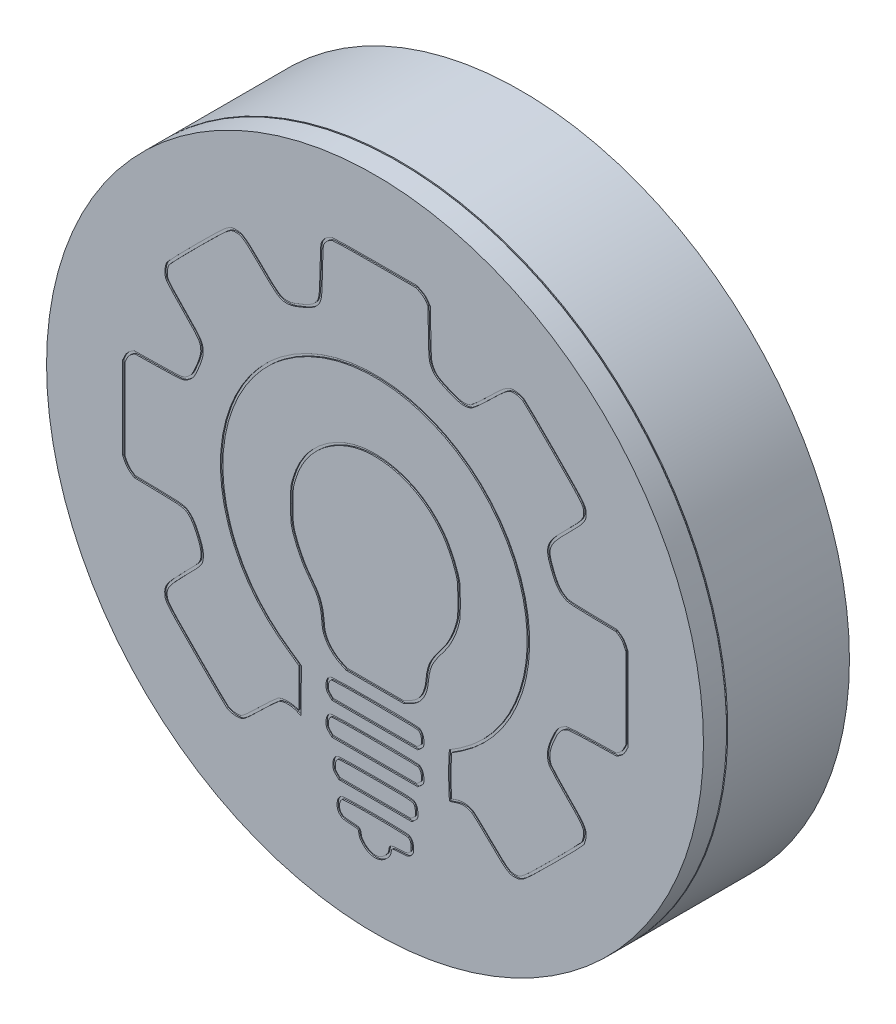
SolidWorks part; units mm, degrees
ref_plane "Front Plane" through (0, 0, 0) normal (0, 0, 1) x (1, 0, 0)
ref_plane "Top Plane" through (0, 0, 0) normal (0, 1, 0) x (1, 0, 0)
ref_plane "Right Plane" through (0, 0, 0) normal (1, 0, 0) x (0, 0, -1)
sketch "Sketch1" plane through (0, 0, 0) normal (0, 0, 1) x (1, 0, 0)
  circle A0 centre (0, 0) radius 25.025
  circle A1 centre (0, 0) radius 27
  dimension "D1" = 50.05
  dimension "D2" = 54
extrude "Boss-Extrude1" add sketch "Sketch1" along normal blind 10
sketch "Sketch2" plane through (0, 0, 10) normal (0, 0, 1) x (1, 0, 0)
  circle A0 centre (0, 0) radius 27
  circle A1 centre (0, 0) radius 27 construction
  point P8 (0, 0)
  circle M3 centre (0, 0) radius 27
  circle M4 centre (0, 0) radius 25.025
extrude "Boss-Extrude3" add sketch "Sketch2" along normal blind 2 contours M3 M4 | M4 region at (-26.2363, 0, 10) region at (0, 0, 10)
sketch "Sketch4" plane through (0, 0, 12) normal (0, 0, 1) x (1, 0, 0)
  line L0 (-17.8576, 4.6203) -> (-19.805, 4.585)
  line L1 (-19.805, 4.585) -> (-20.1013, 4.3874)
  line L2 (-20.574, 3.823) -> (-20.7433, 3.4561)
  line L3 (-20.7433, 3.4561) -> (-20.7433, 0.0624)
  line L4 (-20.7433, 0.0624) -> (-20.7433, -3.3243)
  line L5 (-20.7433, -3.3243) -> (-20.567, -3.6841)
  line L6 (-20.0942, -4.2415) -> (-19.805, -4.4461)
  line L7 (-19.805, -4.4461) -> (-17.8576, -4.4814)
  line L8 (-6.3994, -14.4086) -> (-6.0678, -14.5638)
  line L9 (-6.0678, -14.5638) -> (-6.0678, -12.7999)
  line L10 (17.9282, -4.4884) -> (19.8755, -4.4461)
  line L11 (19.8755, -4.4461) -> (20.1577, -4.2556)
  line L12 (20.6305, -3.6982) -> (20.8139, -3.3243)
  line L13 (20.8139, -3.3243) -> (20.8139, 0.0624)
  line L14 (20.8139, 0.0624) -> (20.8139, 3.4561)
  line L15 (20.8139, 3.4561) -> (20.6446, 3.823)
  line L16 (20.1718, 4.3874) -> (19.8755, 4.585)
  line L17 (19.8755, 4.585) -> (17.9282, 4.6203)
  line L18 (4.5861, 17.9976) -> (4.5508, 19.9097)
  line L19 (4.5508, 19.9097) -> (4.3603, 20.1919)
  line L20 (3.8029, 20.6646) -> (3.429, 20.8481)
  line L21 (3.429, 20.8481) -> (0.0423, 20.841)
  line L22 (-2.8363, -9.2298) -> (-2.3636, -9.4556)
  line L23 (-2.3636, -9.4556) -> (0, -9.4556)
  line L24 (0, -9.4556) -> (2.3636, -9.4556)
  line L25 (2.3636, -9.4556) -> (2.8363, -9.2298)
  line L26 (-3.7818, -11.9321) -> (-3.5419, -12.1719)
  line L27 (-3.5419, -12.1719) -> (-0.0071, -12.1719)
  line L28 (-0.0071, -12.1719) -> (3.5207, -12.1719)
  line L29 (3.5207, -12.1719) -> (3.7747, -11.9532)
  line L30 (-3.7818, -14.5629) -> (-3.5419, -14.8028)
  line L31 (-3.5419, -14.8028) -> (-0.0071, -14.8028)
  line L32 (-0.0071, -14.8028) -> (3.5207, -14.8028)
  line L33 (3.5207, -14.8028) -> (3.7747, -14.5841)
  line L34 (-3.2173, -17.2943) -> (-2.9774, -17.5342)
  line L35 (-2.9774, -17.5342) -> (0.0282, -17.5342)
  line L36 (0.0282, -17.5342) -> (3.0268, -17.5342)
  line L37 (3.0268, -17.5342) -> (3.2808, -17.3155)
  line L76 (-17.854, 4.4203) -> (-19.7428, 4.3861)
  line L77 (-19.7428, 4.3861) -> (-19.989, 4.2219)
  line L78 (-20.3932, 3.7376) -> (-20.5433, 3.4122)
  line L79 (-20.5433, 3.4122) -> (-20.5433, 0.0624)
  line L80 (-20.5433, 0.0624) -> (-20.5433, -3.2779)
  line L81 (-20.5433, -3.2779) -> (-20.3881, -3.5947)
  line L82 (-19.9817, -4.0761) -> (-19.7398, -4.2473)
  line L83 (-19.7398, -4.2473) -> (-17.854, -4.2814)
  line L84 (-6.3165, -14.2265) -> (-6.2678, -14.2493)
  line L85 (-6.2678, -14.2493) -> (-6.2678, -12.7999)
  line L86 (17.9238, -4.2885) -> (19.8124, -4.2474)
  line L87 (19.8124, -4.2474) -> (20.0471, -4.089)
  line L88 (20.4516, -3.6088) -> (20.6139, -3.2779)
  line L89 (20.6139, -3.2779) -> (20.6139, 0.0624)
  line L90 (20.6139, 0.0624) -> (20.6139, 3.4122)
  line L91 (20.6139, 3.4122) -> (20.4637, 3.7376)
  line L92 (20.0596, 4.2219) -> (19.8133, 4.3861)
  line L93 (19.8133, 4.3861) -> (17.9243, 4.4203)
  line L94 (4.3861, 17.9939) -> (4.352, 19.8468)
  line L95 (4.352, 19.8468) -> (4.1937, 20.0812)
  line L96 (3.7135, 20.4857) -> (3.3828, 20.648)
  line L97 (3.3828, 20.648) -> (0.0423, 20.641)
  line L98 (-2.7503, -9.0492) -> (-2.3183, -9.2556)
  line L99 (-2.3183, -9.2556) -> (0, -9.2556)
  line L100 (0, -9.2556) -> (2.3183, -9.2556)
  line L101 (2.3183, -9.2556) -> (2.7507, -9.0491)
  line L102 (-3.6404, -11.7906) -> (-3.459, -11.9719)
  line L103 (-3.459, -11.9719) -> (-0.0071, -11.9719)
  line L104 (-0.0071, -11.9719) -> (3.4465, -11.9719)
  line L105 (3.4465, -11.9719) -> (3.6424, -11.8032)
  line L106 (-3.6404, -14.4215) -> (-3.459, -14.6028)
  line L107 (-3.459, -14.6028) -> (-0.0071, -14.6028)
  line L108 (-0.0071, -14.6028) -> (3.4465, -14.6028)
  line L109 (3.4465, -14.6028) -> (3.6424, -14.4341)
  line L110 (-3.0759, -17.1529) -> (-2.8946, -17.3342)
  line L111 (-2.8946, -17.3342) -> (0.0282, -17.3342)
  line L112 (0.0282, -17.3342) -> (2.9526, -17.3342)
  line L113 (2.9526, -17.3342) -> (3.1485, -17.1655)
  spline S0 degree 3 poles (-3.5631, 20.7634) (-3.8876, 20.6435) (-4.1346, 20.4459) (-4.318, 20.1566) knots 0 0 0 0 1 1 1 1
  spline S1 degree 3 poles (-4.318, 20.1566) (-4.4732, 19.9026) (-4.4803, 19.825) (-4.5156, 17.9906) knots 0 0 0 0 1 1 1 1
  spline S2 degree 3 poles (-4.5156, 17.9906) (-4.5579, 15.888) (-4.5791, 15.7822) (-5.0236, 15.3377) knots 0 0 0 0 1 1 1 1
  spline S3 degree 3 poles (-5.0236, 15.3377) (-5.3128, 15.0413) (-6.5758, 14.4981) (-7.0767, 14.4416) knots 0 0 0 0 1 1 1 1
  spline S4 degree 3 poles (-7.0767, 14.4416) (-7.6976, 14.3781) (-7.9163, 14.5263) (-9.2851, 15.888) knots 0 0 0 0 1 1 1 1
  spline S5 degree 3 poles (-9.2851, 15.888) (-10.5622, 17.158) (-10.8797, 17.3838) (-11.3595, 17.3908) knots 0 0 0 0 1 1 1 1
  spline S6 degree 3 poles (-11.3595, 17.3908) (-12.0086, 17.3908) (-12.0297, 17.3767) (-14.5556, 14.865) knots 0 0 0 0 1 1 1 1
  spline S7 degree 3 poles (-14.5556, 14.865) (-15.868, 13.5526) (-17.0039, 12.3885) (-17.0815, 12.2615) knots 0 0 0 0 1 1 1 1
  spline S8 degree 3 poles (-17.0815, 12.2615) (-17.265, 11.9651) (-17.3285, 11.4148) (-17.2156, 11.0691) knots 0 0 0 0 1 1 1 1
  spline S9 degree 3 poles (-17.2156, 11.0691) (-17.145, 10.8645) (-16.7852, 10.4482) (-15.7974, 9.4463) knots 0 0 0 0 1 1 1 1
  spline S10 degree 3 poles (-15.7974, 9.4463) (-14.3933, 8.0211) (-14.3228, 7.9152) (-14.3228, 7.252) knots 0 0 0 0 1 1 1 1
  spline S11 degree 3 poles (-14.3228, 7.252) (-14.3228, 6.871) (-14.8378, 5.5657) (-15.113, 5.22) knots 0 0 0 0 1 1 1 1
  spline S12 degree 3 poles (-15.113, 5.22) (-15.233, 5.0859) (-15.4587, 4.8954) (-15.614, 4.8108) knots 0 0 0 0 1 1 1 1
  spline S13 degree 3 poles (-15.614, 4.8108) (-15.8962, 4.6697) (-16.0232, 4.6556) (-17.8576, 4.6203) knots 0 0 0 0 1 1 1 1
  spline S14 degree 3 poles (-20.1013, 4.3874) (-20.3059, 4.2463) (-20.4541, 4.077) (-20.574, 3.823) knots 0 0 0 0 1 1 1 1
  spline S15 degree 3 poles (-20.567, -3.6841) (-20.4541, -3.9099) (-20.2777, -4.1216) (-20.0942, -4.2415) knots 0 0 0 0 1 1 1 1
  spline S16 degree 3 poles (-17.8576, -4.4814) (-15.6563, -4.5237) (-15.5857, -4.5378) (-15.1412, -5.0529) knots 0 0 0 0 1 1 1 1
  spline S17 degree 3 poles (-15.1412, -5.0529) (-14.859, -5.3845) (-14.4216, -6.3441) (-14.3298, -6.8591) knots 0 0 0 0 1 1 1 1
  spline S18 degree 3 poles (-14.3298, -6.8591) (-14.2946, -7.0355) (-14.3016, -7.3036) (-14.3369, -7.5012) knots 0 0 0 0 1 1 1 1
  spline S19 degree 3 poles (-14.3369, -7.5012) (-14.4075, -7.8046) (-14.5133, -7.9386) (-15.7057, -9.1381) knots 0 0 0 0 1 1 1 1
  spline S20 degree 3 poles (-15.7057, -9.1381) (-17.0392, -10.4857) (-17.2791, -10.8243) (-17.2861, -11.3182) knots 0 0 0 0 1 1 1 1
  spline S21 degree 3 poles (-17.2861, -11.3182) (-17.2861, -11.9603) (-17.2579, -11.9956) (-14.7532, -14.5215) knots 0 0 0 0 1 1 1 1
  spline S22 degree 3 poles (-14.7532, -14.5215) (-13.4479, -15.8338) (-12.2837, -16.9697) (-12.1567, -17.0473) knots 0 0 0 0 1 1 1 1
  spline S23 degree 3 poles (-12.1567, -17.0473) (-11.8604, -17.2308) (-11.3101, -17.2943) (-10.9643, -17.1814) knots 0 0 0 0 1 1 1 1
  spline S24 degree 3 poles (-10.9643, -17.1814) (-10.7597, -17.1179) (-10.3576, -16.7651) (-9.3839, -15.8056) knots 0 0 0 0 1 1 1 1
  spline S25 degree 3 poles (-9.3839, -15.8056) (-8.6642, -15.1) (-7.9657, -14.458) (-7.8317, -14.3874) knots 0 0 0 0 1 1 1 1
  spline S26 degree 3 poles (-7.8317, -14.3874) (-7.4859, -14.204) (-6.8298, -14.2181) (-6.3994, -14.4086) knots 0 0 0 0 1 1 1 1
  spline S27 degree 3 poles (-6.0678, -12.7999) (-6.0678, -11.8333) (-6.0607, -11.0219) (-6.0537, -10.9866) knots 0 0 0 0 1 1 1 1
  spline S28 degree 3 poles (-6.0537, -10.9866) (-6.0537, -10.9584) (-6.4135, -10.6903) (-6.8651, -10.3869) knots 0 0 0 0 1 1 1 1
  spline S29 degree 3 poles (-6.8651, -10.3869) (-9.3133, -8.75) (-10.9785, -6.5769) (-11.8816, -3.8393) knots 0 0 0 0 1 1 1 1
  spline S30 degree 3 poles (-11.8816, -3.8393) (-13.5608, 1.2195) (-11.7969, 6.864) (-7.5424, 10.0672) knots 0 0 0 0 1 1 1 1
  spline S31 degree 3 poles (-7.5424, 10.0672) (-3.3796, 13.1928) (2.2366, 13.4327) (6.6675, 10.6669) knots 0 0 0 0 1 1 1 1
  spline S32 degree 3 poles (6.6675, 10.6669) (11.5006, 7.6542) (13.6807, 1.6217) (11.8886, -3.8111) knots 0 0 0 0 1 1 1 1
  spline S33 degree 3 poles (11.8886, -3.8111) (11.0067, -6.5063) (9.2992, -8.7571) (6.9427, -10.3375) knots 0 0 0 0 1 1 1 1
  spline S34 degree 3 poles (6.9427, -10.3375) (6.5476, -10.5986) (6.1948, -10.8243) (6.1454, -10.8384) knots 0 0 0 0 1 1 1 1
  spline S35 degree 3 poles (6.1454, -10.8384) (6.0184, -10.8808) (6.0254, -14.5426) (6.1524, -14.5215) knots 0 0 0 0 1 1 1 1
  spline S36 degree 3 poles (6.1524, -14.5215) (6.2018, -14.5144) (6.4347, -14.4368) (6.6675, -14.3592) knots 0 0 0 0 1 1 1 1
  spline S37 degree 3 poles (6.6675, -14.3592) (7.1261, -14.1898) (7.5424, -14.211) (7.9375, -14.4086) knots 0 0 0 0 1 1 1 1
  spline S38 degree 3 poles (7.9375, -14.4086) (8.0504, -14.4721) (8.7207, -15.0859) (9.4192, -15.7773) knots 0 0 0 0 1 1 1 1
  spline S39 degree 3 poles (9.4192, -15.7773) (10.7033, -17.0473) (10.9855, -17.252) (11.4371, -17.252) knots 0 0 0 0 1 1 1 1
  spline S40 degree 3 poles (11.4371, -17.252) (12.065, -17.252) (12.1144, -17.2167) (14.6262, -14.719) knots 0 0 0 0 1 1 1 1
  spline S41 degree 3 poles (14.6262, -14.719) (15.9385, -13.4137) (17.0745, -12.2496) (17.1521, -12.1226) knots 0 0 0 0 1 1 1 1
  spline S42 degree 3 poles (17.1521, -12.1226) (17.2297, -12.0026) (17.3073, -11.7416) (17.3355, -11.544) knots 0 0 0 0 1 1 1 1
  spline S43 degree 3 poles (17.3355, -11.544) (17.4131, -10.8878) (17.272, -10.6762) (15.8538, -9.2509) knots 0 0 0 0 1 1 1 1
  spline S44 degree 3 poles (15.8538, -9.2509) (15.106, -8.5031) (14.5415, -7.8751) (14.478, -7.734) knots 0 0 0 0 1 1 1 1
  spline S45 degree 3 poles (14.478, -7.734) (14.2946, -7.2966) (14.344, -6.845) (14.6403, -6.1042) knots 0 0 0 0 1 1 1 1
  spline S46 degree 3 poles (14.6403, -6.1042) (15.0354, -5.1305) (15.2471, -4.8553) (15.8045, -4.6084) knots 0 0 0 0 1 1 1 1
  spline S47 degree 3 poles (15.8045, -4.6084) (15.9103, -4.559) (16.7287, -4.5096) (17.9282, -4.4884) knots 0 0 0 0 1 1 1 1
  spline S48 degree 3 poles (20.1577, -4.2556) (20.3412, -4.1357) (20.5105, -3.9381) (20.6305, -3.6982) knots 0 0 0 0 1 1 1 1
  spline S49 degree 3 poles (20.6446, 3.823) (20.5246, 4.077) (20.3765, 4.2463) (20.1718, 4.3874) knots 0 0 0 0 1 1 1 1
  spline S50 degree 3 poles (17.9282, 4.6203) (16.0937, 4.6556) (15.9667, 4.6697) (15.6845, 4.8108) knots 0 0 0 0 1 1 1 1
  spline S51 degree 3 poles (15.6845, 4.8108) (15.2612, 5.0366) (15.0142, 5.3823) (14.6826, 6.2078) knots 0 0 0 0 1 1 1 1
  spline S52 degree 3 poles (14.6826, 6.2078) (14.1393, 7.5766) (14.2311, 7.8306) (15.9103, 9.4886) knots 0 0 0 0 1 1 1 1
  spline S53 degree 3 poles (15.9103, 9.4886) (17.1168, 10.681) (17.3496, 10.9985) (17.3567, 11.4571) knots 0 0 0 0 1 1 1 1
  spline S54 degree 3 poles (17.3567, 11.4571) (17.3567, 12.0992) (17.3285, 12.1345) (14.8237, 14.6603) knots 0 0 0 0 1 1 1 1
  spline S55 degree 3 poles (14.8237, 14.6603) (13.5185, 15.9727) (12.3543, 17.1086) (12.2273, 17.1862) knots 0 0 0 0 1 1 1 1
  spline S56 degree 3 poles (12.2273, 17.1862) (12.1073, 17.2638) (11.8463, 17.3415) (11.6487, 17.3697) knots 0 0 0 0 1 1 1 1
  spline S57 degree 3 poles (11.6487, 17.3697) (10.9926, 17.4473) (10.7668, 17.3062) (9.3486, 15.9021) knots 0 0 0 0 1 1 1 1
  spline S58 degree 3 poles (9.3486, 15.9021) (8.5725, 15.1401) (7.9728, 14.6039) (7.8105, 14.5333) knots 0 0 0 0 1 1 1 1
  spline S59 degree 3 poles (7.8105, 14.5333) (7.3801, 14.357) (7.0203, 14.3993) (6.1807, 14.745) knots 0 0 0 0 1 1 1 1
  spline S60 degree 3 poles (6.1807, 14.745) (5.2564, 15.126) (5.0024, 15.3024) (4.7907, 15.7469) knots 0 0 0 0 1 1 1 1
  spline S61 degree 3 poles (4.7907, 15.7469) (4.6284, 16.0715) (4.6214, 16.1702) (4.5861, 17.9976) knots 0 0 0 0 1 1 1 1
  spline S62 degree 3 poles (4.3603, 20.1919) (4.2404, 20.3753) (4.0428, 20.5447) (3.8029, 20.6646) knots 0 0 0 0 1 1 1 1
  spline S63 degree 3 poles (0.0423, 20.841) (-2.1661, 20.841) (-3.429, 20.8128) (-3.5631, 20.7634) knots 0 0 0 0 1 1 1 1
  spline S64 degree 3 poles (-1.0231, 7.0827) (-2.8998, 6.8146) (-4.7413, 5.6363) (-5.8279, 4.0135) knots 0 0 0 0 1 1 1 1
  spline S65 degree 3 poles (-5.8279, 4.0135) (-6.2653, 3.3503) (-6.4911, 2.8705) (-6.7522, 2.0168) knots 0 0 0 0 1 1 1 1
  spline S66 degree 3 poles (-6.7522, 2.0168) (-6.9286, 1.4523) (-6.9427, 1.3183) (-6.9427, 0.1047) knots 0 0 0 0 1 1 1 1
  spline S67 degree 3 poles (-6.9427, 0.1047) (-6.9427, -1.1229) (-6.9286, -1.2429) (-6.7522, -1.8285) knots 0 0 0 0 1 1 1 1
  spline S68 degree 3 poles (-6.7522, -1.8285) (-6.5052, -2.6258) (-5.9619, -3.6841) (-5.5174, -4.2344) knots 0 0 0 0 1 1 1 1
  spline S69 degree 3 poles (-5.5174, -4.2344) (-4.6849, -5.2787) (-4.4732, -5.7584) (-4.3815, -6.8591) knots 0 0 0 0 1 1 1 1
  spline S70 degree 3 poles (-4.3815, -6.8591) (-4.3392, -7.4165) (-4.2827, -7.6634) (-4.1346, -7.9668) knots 0 0 0 0 1 1 1 1
  spline S71 degree 3 poles (-4.1346, -7.9668) (-3.8664, -8.5101) (-3.4008, -8.9617) (-2.8363, -9.2298) knots 0 0 0 0 1 1 1 1
  spline S72 degree 3 poles (2.8363, -9.2298) (3.7959, -8.7782) (4.2827, -8.0374) (4.3886, -6.8662) knots 0 0 0 0 1 1 1 1
  spline S73 degree 3 poles (4.3886, -6.8662) (4.4873, -5.7937) (4.699, -5.3351) (5.6797, -4.0933) knots 0 0 0 0 1 1 1 1
  spline S74 degree 3 poles (5.6797, -4.0933) (6.1454, -3.5007) (6.5546, -2.6963) (6.8157, -1.8356) knots 0 0 0 0 1 1 1 1
  spline S75 degree 3 poles (6.8157, -1.8356) (6.9991, -1.2358) (7.0132, -1.1229) (7.0132, 0.1047) knots 0 0 0 0 1 1 1 1
  spline S76 degree 3 poles (7.0132, 0.1047) (7.0132, 1.3253) (6.9991, 1.4523) (6.8227, 2.0309) knots 0 0 0 0 1 1 1 1
  spline S77 degree 3 poles (6.8227, 2.0309) (6.5899, 2.7858) (6.1242, 3.7313) (5.6938, 4.3098) knots 0 0 0 0 1 1 1 1
  spline S78 degree 3 poles (5.6938, 4.3098) (4.1698, 6.3771) (1.5663, 7.4496) (-1.0231, 7.0827) knots 0 0 0 0 1 1 1 1
  spline S79 degree 3 poles (-3.6336, -10.5633) (-3.9088, -10.7114) (-4.0217, -10.9231) (-4.0217, -11.3112) knots 0 0 0 0 1 1 1 1
  spline S80 degree 3 poles (-4.0217, -11.3112) (-4.0217, -11.6498) (-3.9934, -11.7204) (-3.7818, -11.9321) knots 0 0 0 0 1 1 1 1
  spline S81 degree 3 poles (3.7747, -11.9532) (3.9934, -11.7557) (4.0217, -11.6992) (4.0217, -11.3817) knots 0 0 0 0 1 1 1 1
  spline S82 degree 3 poles (4.0217, -11.3817) (4.0217, -10.9654) (3.8876, -10.6762) (3.6336, -10.5633) knots 0 0 0 0 1 1 1 1
  spline S83 degree 3 poles (3.6336, -10.5633) (3.3867, -10.4504) (-3.429, -10.4433) (-3.6336, -10.5633) knots 0 0 0 0 1 1 1 1
  spline S84 degree 3 poles (-3.6336, -13.1941) (-3.9088, -13.3423) (-4.0217, -13.554) (-4.0217, -13.942) knots 0 0 0 0 1 1 1 1
  spline S85 degree 3 poles (-4.0217, -13.942) (-4.0217, -14.2807) (-3.9934, -14.3513) (-3.7818, -14.5629) knots 0 0 0 0 1 1 1 1
  spline S86 degree 3 poles (3.7747, -14.5841) (3.9934, -14.3865) (4.0217, -14.3301) (4.0217, -14.0126) knots 0 0 0 0 1 1 1 1
  spline S87 degree 3 poles (4.0217, -14.0126) (4.0217, -13.6104) (3.8664, -13.3) (3.6195, -13.1871) knots 0 0 0 0 1 1 1 1
  spline S88 degree 3 poles (3.6195, -13.1871) (3.3796, -13.0813) (-3.4361, -13.0813) (-3.6336, -13.1941) knots 0 0 0 0 1 1 1 1
  spline S89 degree 3 poles (-3.0692, -15.9255) (-3.3443, -16.0737) (-3.4572, -16.2853) (-3.4572, -16.6734) knots 0 0 0 0 1 1 1 1
  spline S90 degree 3 poles (-3.4572, -16.6734) (-3.4572, -17.0121) (-3.429, -17.0826) (-3.2173, -17.2943) knots 0 0 0 0 1 1 1 1
  spline S91 degree 3 poles (3.2808, -17.3155) (3.4996, -17.1179) (3.5278, -17.0544) (3.5278, -16.751) knots 0 0 0 0 1 1 1 1
  spline S92 degree 3 poles (3.5278, -16.751) (3.5278, -16.5676) (3.4925, -16.3277) (3.4431, -16.2289) knots 0 0 0 0 1 1 1 1
  spline S93 degree 3 poles (3.4431, -16.2289) (3.2667, -15.8479) (3.2173, -15.8408) (0.0212, -15.8408) knots 0 0 0 0 1 1 1 1
  spline S94 degree 3 poles (0.0212, -15.8408) (-1.9897, -15.8479) (-2.9704, -15.8691) (-3.0692, -15.9255) knots 0 0 0 0 1 1 1 1
  spline S95 degree 3 poles (-2.7376, -18.6137) (-2.9845, -18.7548) (-3.1044, -18.9735) (-3.1115, -19.3122) knots 0 0 0 0 1 1 1 1
  spline S96 degree 3 poles (-3.1115, -19.3122) (-3.1256, -19.6508) (-3.0551, -19.8272) (-2.8222, -20.0389) knots 0 0 0 0 1 1 1 1
  spline S97 degree 3 poles (-2.8222, -20.0389) (-2.7023, -20.1518) (-2.5329, -20.1871) (-2.0249, -20.2153) knots 0 0 0 0 1 1 1 1
  spline S98 degree 3 poles (-2.0249, -20.2153) (-1.4464, -20.2435) (-1.3758, -20.2647) (-1.3547, -20.3917) knots 0 0 0 0 1 1 1 1
  spline S99 degree 3 poles (-1.3547, -20.3917) (-1.3053, -20.7515) (-1.2559, -20.8644) (-1.0372, -21.1043) knots 0 0 0 0 1 1 1 1
  spline S100 degree 3 poles (-1.0372, -21.1043) (-0.4516, -21.7816) (0.4516, -21.7816) (1.0372, -21.1043) knots 0 0 0 0 1 1 1 1
  spline S101 degree 3 poles (1.0372, -21.1043) (1.2559, -20.8644) (1.3053, -20.7515) (1.3547, -20.3917) knots 0 0 0 0 1 1 1 1
  spline S102 degree 3 poles (1.3547, -20.3917) (1.3758, -20.2647) (1.4464, -20.2506) (2.0602, -20.2153) knots 0 0 0 0 1 1 1 1
  spline S103 degree 3 poles (2.0602, -20.2153) (2.6952, -20.18) (2.7587, -20.1659) (2.9563, -19.9754) knots 0 0 0 0 1 1 1 1
  spline S104 degree 3 poles (2.9563, -19.9754) (3.1397, -19.799) (3.175, -19.7143) (3.175, -19.4321) knots 0 0 0 0 1 1 1 1
  spline S105 degree 3 poles (3.175, -19.4321) (3.175, -19.0088) (3.0621, -18.7477) (2.8152, -18.6207) knots 0 0 0 0 1 1 1 1
  spline S106 degree 3 poles (2.8152, -18.6207) (2.5471, -18.4867) (-2.4906, -18.4796) (-2.7376, -18.6137) knots 0 0 0 0 1 1 1 1
  spline S107 degree 1 poles (-19.989, 4.2219) (-20.3932, 3.7376) knots 0 0 1 1 construction
  spline S108 degree 1 poles (-20.3881, -3.5947) (-19.9817, -4.0761) knots 0 0 1 1 construction
  spline S109 degree 1 poles (-17.854, -4.2814) (-14.9894, -4.9227) knots 0 0 1 1 construction
  spline S110 degree 1 poles (-14.9894, -4.9227) (-14.1333, -6.822) knots 0 0 1 1 construction
  spline S111 degree 1 poles (-14.1333, -6.822) (-14.1409, -7.5414) knots 0 0 1 1 construction
  spline S112 degree 1 poles (-14.1409, -7.5414) (-15.5637, -9.2789) knots 0 0 1 1 construction
  spline S113 degree 1 poles (-15.5637, -9.2789) (-17.0861, -11.3197) knots 0 0 1 1 construction
  spline S114 degree 1 poles (-17.0861, -11.3197) (-14.6113, -14.3805) knots 0 0 1 1 construction
  spline S115 degree 1 poles (-14.6113, -14.3805) (-12.0501, -16.8781) knots 0 0 1 1 construction
  spline S116 degree 1 poles (-12.0501, -16.8781) (-11.025, -16.9908) knots 0 0 1 1 construction
  spline S117 degree 1 poles (-11.025, -16.9908) (-9.5241, -15.6629) knots 0 0 1 1 construction
  spline S118 degree 1 poles (-9.5241, -15.6629) (-7.9252, -14.2106) knots 0 0 1 1 construction
  spline S119 degree 1 poles (-7.9252, -14.2106) (-6.3165, -14.2265) knots 0 0 1 1 construction
  spline S120 degree 1 poles (-6.2678, -12.7999) (-6.2573, -11.0672) knots 0 0 1 1 construction
  spline S121 degree 1 poles (-6.2573, -11.0672) (-6.9764, -10.553) knots 0 0 1 1 construction
  spline S122 degree 1 poles (-6.9764, -10.553) (-12.0714, -3.9022) knots 0 0 1 1 construction
  spline S123 degree 1 poles (-12.0714, -3.9022) (-7.6626, 10.227) knots 0 0 1 1 construction
  spline S124 degree 1 poles (-7.6626, 10.227) (6.7734, 10.8366) knots 0 0 1 1 construction
  spline S125 degree 1 poles (6.7734, 10.8366) (12.0786, -3.8735) knots 0 0 1 1 construction
  spline S126 degree 1 poles (12.0786, -3.8735) (7.0535, -10.504) knots 0 0 1 1 construction
  spline S127 degree 1 poles (7.0535, -10.504) (6.3095, -10.9791) knots 0 0 1 1 construction
  spline S128 degree 1 poles (6.3095, -10.9791) (6.3008, -14.2697) knots 0 0 1 1 construction
  spline S129 degree 1 poles (6.3008, -14.2697) (6.6013, -14.1704) knots 0 0 1 1 construction
  spline S130 degree 1 poles (6.6013, -14.1704) (8.0313, -14.2319) knots 0 0 1 1 construction
  spline S131 degree 1 poles (8.0313, -14.2319) (9.5598, -15.6352) knots 0 0 1 1 construction
  spline S132 degree 1 poles (9.5598, -15.6352) (11.4371, -17.052) knots 0 0 1 1 construction
  spline S133 degree 1 poles (11.4371, -17.052) (14.4851, -14.5772) knots 0 0 1 1 construction
  spline S134 degree 1 poles (14.4851, -14.5772) (16.9828, -12.0161) knots 0 0 1 1 construction
  spline S135 degree 1 poles (16.9828, -12.0161) (17.1372, -11.5181) knots 0 0 1 1 construction
  spline S136 degree 1 poles (17.1372, -11.5181) (15.7122, -9.3922) knots 0 0 1 1 construction
  spline S137 degree 1 poles (15.7122, -9.3922) (14.2946, -7.8137) knots 0 0 1 1 construction
  spline S138 degree 1 poles (14.2946, -7.8137) (14.4548, -6.0294) knots 0 0 1 1 construction
  spline S139 degree 1 poles (14.4548, -6.0294) (15.7222, -4.4261) knots 0 0 1 1 construction
  spline S140 degree 1 poles (15.7222, -4.4261) (17.9238, -4.2885) knots 0 0 1 1 construction
  spline S141 degree 1 poles (20.0471, -4.089) (20.4516, -3.6088) knots 0 0 1 1 construction
  spline S142 degree 1 poles (20.4637, 3.7376) (20.0596, 4.2219) knots 0 0 1 1 construction
  spline S143 degree 1 poles (17.9243, 4.4203) (15.5927, 4.6331) knots 0 0 1 1 construction
  spline S144 degree 1 poles (15.5927, 4.6331) (14.4969, 6.1336) knots 0 0 1 1 construction
  spline S145 degree 1 poles (14.4969, 6.1336) (15.7697, 9.6309) knots 0 0 1 1 construction
  spline S146 degree 1 poles (15.7697, 9.6309) (17.1567, 11.4587) knots 0 0 1 1 construction
  spline S147 degree 1 poles (17.1567, 11.4587) (14.6818, 14.5194) knots 0 0 1 1 construction
  spline S148 degree 1 poles (14.6818, 14.5194) (12.1208, 17.0169) knots 0 0 1 1 construction
  spline S149 degree 1 poles (12.1208, 17.0169) (11.6228, 17.1714) knots 0 0 1 1 construction
  spline S150 degree 1 poles (11.6228, 17.1714) (9.489, 15.7597) knots 0 0 1 1 construction
  spline S151 degree 1 poles (9.489, 15.7597) (7.8883, 14.3491) knots 0 0 1 1 construction
  spline S152 degree 1 poles (7.8883, 14.3491) (6.1045, 14.5601) knots 0 0 1 1 construction
  spline S153 degree 1 poles (6.1045, 14.5601) (4.611, 15.6592) knots 0 0 1 1 construction
  spline S154 degree 1 poles (4.611, 15.6592) (4.3861, 17.9939) knots 0 0 1 1 construction
  spline S155 degree 1 poles (4.1937, 20.0812) (3.7135, 20.4857) knots 0 0 1 1 construction
  spline S156 degree 1 poles (0.0423, 20.641) (-3.4992, 20.5738) knots 0 0 1 1 construction
  spline S157 degree 1 poles (-3.4992, 20.5738) (-4.1482, 20.0509) knots 0 0 1 1 construction
  spline S158 degree 1 poles (-4.1482, 20.0509) (-4.3156, 17.9866) knots 0 0 1 1 construction
  spline S159 degree 1 poles (-4.3156, 17.9866) (-4.8814, 15.197) knots 0 0 1 1 construction
  spline S160 degree 1 poles (-4.8814, 15.197) (-7.0554, 14.2428) knots 0 0 1 1 construction
  spline S161 degree 1 poles (-7.0554, 14.2428) (-9.4262, 15.7462) knots 0 0 1 1 construction
  spline S162 degree 1 poles (-9.4262, 15.7462) (-11.361, 17.1908) knots 0 0 1 1 construction
  spline S163 degree 1 poles (-11.361, 17.1908) (-14.4144, 14.7233) knots 0 0 1 1 construction
  spline S164 degree 1 poles (-14.4144, 14.7233) (-16.9123, 12.1549) knots 0 0 1 1 construction
  spline S165 degree 1 poles (-16.9123, 12.1549) (-17.026, 11.1329) knots 0 0 1 1 construction
  spline S166 degree 1 poles (-17.026, 11.1329) (-15.655, 9.5867) knots 0 0 1 1 construction
  spline S167 degree 1 poles (-15.655, 9.5867) (-14.1228, 7.252) knots 0 0 1 1 construction
  spline S168 degree 1 poles (-14.1228, 7.252) (-14.9601, 5.0909) knots 0 0 1 1 construction
  spline S169 degree 1 poles (-14.9601, 5.0909) (-15.5213, 4.6335) knots 0 0 1 1 construction
  spline S170 degree 1 poles (-15.5213, 4.6335) (-17.854, 4.4203) knots 0 0 1 1 construction
  spline S171 degree 3 poles (-19.989, 4.2219) (-20.0319, 4.1923) (-20.1163, 4.1267) (-20.2192, 4.0206) (-20.3099, 3.8978) (-20.3682, 3.7904) (-20.3932, 3.7376) knots 0.002323 0.002323 0.002323 0.002323 0.251742 0.501161 0.750581 1 1 1 1
  spline S172 degree 3 poles (-20.3881, -3.5947) (-20.363, -3.6448) (-20.3067, -3.7417) (-20.2049, -3.8781) (-20.0918, -3.9953) (-20.0211, -4.0504) (-19.9817, -4.0761) knots 0 0 0 0 0.25139 0.502779 0.754169 1.005559 1.005559 1.005559 1.005559
  spline S173 degree 3 poles (-17.854, -4.2814) (-17.7244, -4.2839) (-17.4538, -4.2892) (-17.0029, -4.2994) (-16.534, -4.3146) (-16.111, -4.3432) (-15.6809, -4.404) (-15.304, -4.5609) (-15.0925, -4.8032) (-14.9894, -4.9227) knots -0.000034 -0.000034 -0.000034 -0.000034 0.062489 0.125013 0.250059 0.375105 0.500152 0.750245 1.000338 1.000338 1.000338 1.000338
  spline S174 degree 3 poles (-14.9894, -4.9227) (-14.9436, -4.9766) (-14.8652, -5.0844) (-14.6914, -5.3691) (-14.4773, -5.7943) (-14.2524, -6.3571) (-14.1628, -6.6573) (-14.1333, -6.822) knots -0.000527 -0.000527 -0.000527 -0.000527 0.124393 0.249313 0.499154 0.748994 0.998835 0.998835 0.998835 0.998835
  spline S175 degree 3 poles (-14.1333, -6.822) (-14.122, -6.8791) (-14.1088, -6.9924) (-14.1045, -7.1793) (-14.1152, -7.3686) (-14.1305, -7.4833) (-14.1409, -7.5414) knots 0.003226 0.003226 0.003226 0.003226 0.25457 0.505915 0.757259 1.008604 1.008604 1.008604 1.008604
  spline S176 degree 3 poles (-14.1409, -7.5414) (-14.1619, -7.6318) (-14.2122, -7.7972) (-14.3793, -8.0379) (-14.6058, -8.2954) (-14.8383, -8.5424) (-15.0974, -8.808) (-15.3454, -9.0591) (-15.4928, -9.2076) (-15.5637, -9.2789) knots -0.005543 -0.005543 -0.005543 -0.005543 0.245831 0.497206 0.622893 0.74858 0.874267 0.937111 0.999954 0.999954 0.999954 0.999954
  spline S177 degree 3 poles (-15.5637, -9.2789) (-15.6427, -9.3587) (-15.806, -9.5245) (-16.0852, -9.8118) (-16.3807, -10.1244) (-16.6485, -10.4272) (-16.9062, -10.7551) (-17.0599, -11.0361) (-17.0846, -11.2203) (-17.0861, -11.3197) knots 0.000041 0.000041 0.000041 0.000041 0.062471 0.124902 0.249763 0.374624 0.499485 0.749207 0.998929 0.998929 0.998929 0.998929
  spline S178 degree 3 poles (-17.0861, -11.3197) (-17.0861, -11.3867) (-17.0844, -11.5355) (-17.0592, -11.6701) (-16.9879, -11.8353) (-16.8223, -12.0734) (-16.5312, -12.4124) (-16.0911, -12.8797) (-15.5728, -13.4093) (-15.0654, -13.9225) (-14.7582, -14.2323) (-14.6113, -14.3805) knots 0.000773 0.000773 0.000773 0.000773 0.125675 0.250576 0.375478 0.50038 0.625281 0.750183 0.875084 0.937535 0.999986 0.999986 0.999986 0.999986
  spline S179 degree 3 poles (-14.6113, -14.3805) (-14.3067, -14.6867) (-13.6667, -15.3261) (-13.0066, -15.9757) (-12.5759, -16.3931) (-12.3149, -16.6415) (-12.1607, -16.7842) (-12.074, -16.8594) (-12.0611, -16.8702) (-12.0501, -16.8781) knots 0.000027 0.000027 0.000027 0.000027 0.244111 0.488195 0.610236 0.732278 0.85432 0.915341 0.976362 0.976362 0.976362 0.976362
  spline S180 degree 3 poles (-12.0501, -16.8781) (-11.9834, -16.9192) (-11.8494, -16.974) (-11.556, -17.0367) (-11.2541, -17.0412) (-11.1028, -17.0162) (-11.025, -16.9908) knots 0.002003 0.002003 0.002003 0.002003 0.251839 0.501675 0.751511 1.001347 1.001347 1.001347 1.001347
  spline S181 degree 3 poles (-11.025, -16.9908) (-11.0073, -16.9853) (-10.9841, -16.9752) (-10.8573, -16.8986) (-10.6225, -16.7104) (-10.2529, -16.3709) (-9.8754, -16.0078) (-9.6367, -15.7739) (-9.5241, -15.6629) knots -0.002287 -0.002287 -0.002287 -0.002287 0.123007 0.248301 0.498888 0.749476 0.87477 1.000063 1.000063 1.000063 1.000063
  spline S182 degree 3 poles (-9.5241, -15.6629) (-9.3489, -15.4912) (-8.9825, -15.1373) (-8.5061, -14.6923) (-8.1964, -14.4159) (-8.0233, -14.2751) (-7.9624, -14.2302) (-7.9252, -14.2106) knots -0.000086 -0.000086 -0.000086 -0.000086 0.249847 0.499779 0.749712 0.874679 0.999645 0.999645 0.999645 0.999645
  spline S183 degree 3 poles (-7.9252, -14.2106) (-7.8113, -14.1502) (-7.5674, -14.0766) (-7.1446, -14.0447) (-6.7091, -14.0913) (-6.4437, -14.1702) (-6.3165, -14.2265) knots 0.000189 0.000189 0.000189 0.000189 0.250515 0.500841 0.751167 1.001494 1.001494 1.001494 1.001494
  spline S184 degree 3 poles (-6.2678, -12.7999) (-6.2678, -12.6085) (-6.2672, -12.2098) (-6.2648, -11.7068) (-6.262, -11.3729) (-6.2593, -11.169) (-6.2581, -11.1043) (-6.2573, -11.0672) knots 0 0 0 0 0.206567 0.413133 0.6197 0.722983 0.826266 0.826266 0.826266 0.826266
  spline S185 degree 3 poles (-6.2573, -11.0672) (-6.2956, -11.0361) (-6.3621, -10.985) (-6.536, -10.8573) (-6.7384, -10.7147) (-6.8988, -10.6052) (-6.9764, -10.553) knots 0.27751 0.27751 0.27751 0.27751 0.458097 0.638685 0.819273 0.99986 0.99986 0.99986 0.99986
  spline S186 degree 3 poles (-6.9764, -10.553) (-7.5808, -10.149) (-8.7469, -9.2354) (-10.1592, -7.682) (-11.2854, -5.9214) (-11.8473, -4.5815) (-12.0714, -3.9022) knots 0.000025 0.000025 0.000025 0.000025 0.250014 0.500002 0.749991 0.999979 0.999979 0.999979 0.999979
  spline S187 degree 3 poles (-12.0714, -3.9022) (-12.2822, -3.2671) (-12.6031, -1.9523) (-12.8135, 0.6761) (-12.3171, 3.9287) (-10.8751, 6.8855) (-9.2077, 8.9267) (-8.1968, 9.8249) (-7.6626, 10.227) knots 0.000011 0.000011 0.000011 0.000011 0.125011 0.250011 0.50001 0.750009 0.875009 1.000008 1.000008 1.000008 1.000008
  spline S188 degree 3 poles (-7.6626, 10.227) (-7.1409, 10.6187) (-6.0277, 11.3284) (-3.6829, 12.3608) (-0.5551, 12.9641) (2.6154, 12.6276) (5.0448, 11.7967) (6.2183, 11.183) (6.7734, 10.8366) knots -0.000008 -0.000008 -0.000008 -0.000008 0.124992 0.249993 0.499994 0.749995 0.874996 0.999996 0.999996 0.999996 0.999996
  spline S189 degree 3 poles (6.7734, 10.8366) (7.3791, 10.459) (8.5348, 9.5901) (10.4582, 7.5449) (12.1619, 4.4806) (12.809, 1.0303) (12.6368, -1.7799) (12.3031, -3.193) (12.0786, -3.8735) knots 0.000004 0.000004 0.000004 0.000004 0.125001 0.249999 0.499995 0.749991 0.874988 0.999986 0.999986 0.999986 0.999986
  spline S190 degree 3 poles (12.0786, -3.8735) (11.8576, -4.5489) (11.3009, -5.8741) (10.174, -7.6485) (8.7696, -9.2131) (7.6439, -10.108) (7.0535, -10.504) knots 0.000028 0.000028 0.000028 0.000028 0.250041 0.500054 0.750068 1.000081 1.000081 1.000081 1.000081
  spline S191 degree 3 poles (7.0535, -10.504) (6.9768, -10.5547) (6.8177, -10.6592) (6.6101, -10.7936) (6.4284, -10.9082) (6.3536, -10.9539) (6.3095, -10.9791) knots -0.000485 -0.000485 -0.000485 -0.000485 0.199236 0.398958 0.598679 0.7984 0.7984 0.7984 0.7984
  spline S192 degree 3 poles (6.3095, -10.9791) (6.3045, -11.0135) (6.2979, -11.0732) (6.2823, -11.2686) (6.268, -11.5801) (6.2569, -12.0396) (6.2526, -12.5435) (6.2548, -13.0569) (6.2636, -13.5447) (6.276, -13.8967) (6.2896, -14.1338) (6.2963, -14.2219) (6.3008, -14.2697) knots 0.098872 0.098872 0.098872 0.098872 0.1454 0.191929 0.284986 0.378043 0.4711 0.564157 0.657214 0.750271 0.796799 0.843328 0.843328 0.843328 0.843328
  spline S193 degree 3 poles (6.3008, -14.2697) (6.3237, -14.2623) (6.3682, -14.2478) (6.4433, -14.223) (6.5211, -14.1971) (6.5747, -14.1793) (6.6013, -14.1704) knots 0.536874 0.536874 0.536874 0.536874 0.651594 0.766314 0.881035 0.995755 0.995755 0.995755 0.995755
  spline S194 degree 3 poles (6.6013, -14.1704) (6.722, -14.126) (6.977, -14.0562) (7.3402, -14.0338) (7.695, -14.0884) (7.9232, -14.1778) (8.0313, -14.2319) knots 0.002041 0.002041 0.002041 0.002041 0.25245 0.50286 0.753269 1.003679 1.003679 1.003679 1.003679
  spline S195 degree 3 poles (8.0313, -14.2319) (8.0628, -14.2496) (8.1133, -14.2865) (8.272, -14.4179) (8.5658, -14.6815) (9.0278, -15.1149) (9.3883, -15.4654) (9.5598, -15.6352) knots -0.012546 -0.012546 -0.012546 -0.012546 0.11402 0.240587 0.493719 0.746852 0.999985 0.999985 0.999985 0.999985
  spline S196 degree 3 poles (9.5598, -15.6352) (9.6359, -15.7104) (9.794, -15.8662) (10.0662, -16.1313) (10.3604, -16.4107) (10.6417, -16.6616) (10.9421, -16.8998) (11.1869, -17.034) (11.3499, -17.052) (11.4371, -17.052) knots 0.000008 0.000008 0.000008 0.000008 0.062508 0.125007 0.250006 0.375005 0.500004 0.750002 1 1 1 1
  spline S197 degree 3 poles (11.4371, -17.052) (11.5027, -17.052) (11.6481, -17.0501) (11.7806, -17.0247) (11.9457, -16.9527) (12.1841, -16.7862) (12.5231, -16.4947) (12.9899, -16.0547) (13.518, -15.537) (14.0292, -15.0304) (14.3376, -14.7239) (14.4851, -14.5772) knots 0 0 0 0 0.125 0.25 0.375 0.499999 0.624999 0.749999 0.874999 0.937499 0.999999 0.999999 0.999999 0.999999
  spline S198 degree 3 poles (14.4851, -14.5772) (14.7912, -14.2728) (15.4302, -13.6332) (16.0795, -12.9734) (16.4969, -12.5427) (16.7454, -12.2816) (16.8883, -12.1273) (16.9637, -12.0403) (16.9747, -12.0271) (16.9828, -12.0161) knots 0.000002 0.000002 0.000002 0.000002 0.243936 0.48787 0.609837 0.731803 0.85377 0.914754 0.975737 0.975737 0.975737 0.975737
  spline S199 degree 3 poles (16.9828, -12.0161) (16.9993, -11.9905) (17.0208, -11.9466) (17.0722, -11.8083) (17.1126, -11.6564) (17.1303, -11.5654) (17.1372, -11.5181) knots -0.00601 -0.00601 -0.00601 -0.00601 0.244357 0.494724 0.745091 0.995458 0.995458 0.995458 0.995458
  spline S200 degree 3 poles (17.1372, -11.5181) (17.1452, -11.4495) (17.1576, -11.3004) (17.1403, -11.092) (17.0578, -10.8812) (16.8249, -10.5655) (16.5633, -10.2663) (16.2611, -9.9487) (15.9695, -9.6512) (15.7958, -9.4762) (15.7122, -9.3922) knots 0.001315 0.001315 0.001315 0.001315 0.126145 0.250976 0.500637 0.625467 0.750298 0.875128 0.937544 0.999959 0.999959 0.999959 0.999959
  spline S201 degree 3 poles (15.7122, -9.3922) (15.5346, -9.2145) (15.163, -8.8344) (14.7376, -8.3795) (14.4274, -8.0148) (14.3333, -7.8999) (14.2946, -7.8137) knots 0.000078 0.000078 0.000078 0.000078 0.251447 0.502815 0.754184 1.005552 1.005552 1.005552 1.005552
  spline S202 degree 3 poles (14.2946, -7.8137) (14.2431, -7.691) (14.1687, -7.4347) (14.1647, -7.0185) (14.2531, -6.5755) (14.3858, -6.202) (14.4548, -6.0294) knots -0.001811 -0.001811 -0.001811 -0.001811 0.248694 0.499199 0.749703 1.000208 1.000208 1.000208 1.000208
  spline S203 degree 3 poles (14.4548, -6.0294) (14.5009, -5.9157) (14.6009, -5.677) (14.775, -5.3054) (14.9948, -4.9395) (15.3081, -4.6336) (15.5835, -4.4876) (15.7222, -4.4261) knots -0.000158 -0.000158 -0.000158 -0.000158 0.124775 0.249708 0.499574 0.74944 0.999307 0.999307 0.999307 0.999307
  spline S204 degree 3 poles (15.7222, -4.4261) (15.8059, -4.388) (15.9525, -4.3767) (16.4136, -4.3358) (16.9625, -4.3129) (17.4827, -4.2973) (17.7799, -4.291) (17.9238, -4.2885) knots 0.001885 0.001885 0.001885 0.001885 0.251357 0.500829 0.750301 0.875037 0.999773 0.999773 0.999773 0.999773
  spline S205 degree 3 poles (20.0471, -4.089) (20.0861, -4.0635) (20.1572, -4.0085) (20.2668, -3.8963) (20.3662, -3.7637) (20.4256, -3.6608) (20.4516, -3.6088) knots -0.002232 -0.002232 -0.002232 -0.002232 0.248326 0.498884 0.749442 1 1 1 1
  spline S206 degree 3 poles (20.4637, 3.7376) (20.4388, 3.7904) (20.3805, 3.8978) (20.2898, 4.0206) (20.1868, 4.1267) (20.1025, 4.1923) (20.0596, 4.2219) knots 0 0 0 0 0.249419 0.498839 0.748258 0.997677 0.997677 0.997677 0.997677
  spline S207 degree 3 poles (17.9243, 4.4203) (17.8158, 4.4224) (17.5897, 4.4268) (17.2107, 4.4349) (16.8152, 4.445) (16.4588, 4.4587) (16.1056, 4.4814) (15.8223, 4.5263) (15.6726, 4.5932) (15.5927, 4.6331) knots 0 0 0 0 0.062674 0.125347 0.250695 0.376042 0.50139 0.752085 1.00278 1.00278 1.00278 1.00278
  spline S208 degree 3 poles (15.5927, 4.6331) (15.4762, 4.6952) (15.2566, 4.842) (14.982, 5.149) (14.7804, 5.4934) (14.6224, 5.8297) (14.5366, 6.0347) (14.4969, 6.1336) knots -0.001828 -0.001828 -0.001828 -0.001828 0.248668 0.499164 0.749659 0.874907 1.000155 1.000155 1.000155 1.000155
  spline S209 degree 3 poles (14.4969, 6.1336) (14.4343, 6.2914) (14.3066, 6.628) (14.1986, 7.0322) (14.1713, 7.4269) (14.2568, 7.8106) (14.4548, 8.1879) (14.7607, 8.5874) (15.1174, 8.9747) (15.4636, 9.3274) (15.6701, 9.5325) (15.7697, 9.6309) knots -0.000094 -0.000094 -0.000094 -0.000094 0.124917 0.249928 0.374939 0.49995 0.624961 0.749972 0.874983 0.937488 0.999994 0.999994 0.999994 0.999994
  spline S210 degree 3 poles (15.7697, 9.6309) (15.9058, 9.7654) (16.1962, 10.0551) (16.5085, 10.3792) (16.7553, 10.6525) (16.9902, 10.9464) (17.1319, 11.2011) (17.1552, 11.3684) (17.1567, 11.4587) knots 0.000009 0.000009 0.000009 0.000009 0.12485 0.249692 0.374533 0.499375 0.749057 0.99874 0.99874 0.99874 0.99874
  spline S211 degree 3 poles (17.1567, 11.4587) (17.1567, 11.5257) (17.155, 11.6745) (17.1298, 11.809) (17.0584, 11.9742) (16.8928, 12.2124) (16.6017, 12.5514) (16.1616, 13.0186) (15.6433, 13.5482) (15.1359, 14.0614) (14.8288, 14.3712) (14.6818, 14.5194) knots 0.000837 0.000837 0.000837 0.000837 0.12573 0.250624 0.375518 0.500411 0.625305 0.750199 0.875092 0.937539 0.999986 0.999986 0.999986 0.999986
  spline S212 degree 3 poles (14.6818, 14.5194) (14.3775, 14.8254) (13.7378, 15.4644) (13.078, 16.1137) (12.6474, 16.5311) (12.3863, 16.7796) (12.232, 16.9225) (12.1451, 16.9979) (12.1318, 17.0089) (12.1208, 17.0169) knots 0.000027 0.000027 0.000027 0.000027 0.243955 0.487882 0.609846 0.73181 0.853773 0.914755 0.975737 0.975737 0.975737 0.975737
  spline S213 degree 3 poles (12.1208, 17.0169) (12.0952, 17.0335) (12.0513, 17.055) (11.913, 17.1064) (11.7611, 17.1467) (11.6701, 17.1645) (11.6228, 17.1714) knots -0.00601 -0.00601 -0.00601 -0.00601 0.244357 0.494724 0.74509 0.995457 0.995457 0.995457 0.995457
  spline S214 degree 3 poles (11.6228, 17.1714) (11.554, 17.1794) (11.4048, 17.1917) (11.1932, 17.1746) (10.9788, 17.0921) (10.6609, 16.8614) (10.3608, 16.6023) (10.0435, 16.3031) (9.7469, 16.0143) (9.5726, 15.8425) (9.489, 15.7597) knots 0.001315 0.001315 0.001315 0.001315 0.12616 0.251004 0.500693 0.625537 0.750381 0.875225 0.937648 1.00007 1.00007 1.00007 1.00007
  spline S215 degree 3 poles (9.489, 15.7597) (9.3074, 15.5813) (8.917, 15.2052) (8.4644, 14.7873) (8.1013, 14.4836) (7.9773, 14.3878) (7.8883, 14.3491) knots -0.000128 -0.000128 -0.000128 -0.000128 0.250901 0.50193 0.752959 1.003988 1.003988 1.003988 1.003988
  spline S216 degree 3 poles (7.8883, 14.3491) (7.7711, 14.301) (7.5269, 14.2273) (7.1344, 14.2269) (6.7603, 14.3163) (6.4139, 14.436) (6.2039, 14.5191) (6.1045, 14.5601) knots -0.001517 -0.001517 -0.001517 -0.001517 0.248866 0.499248 0.749631 0.874823 1.000014 1.000014 1.000014 1.000014
  spline S217 degree 3 poles (6.1045, 14.5601) (5.9972, 14.6043) (5.7712, 14.6997) (5.4221, 14.8608) (5.0824, 15.0533) (4.7971, 15.3183) (4.6663, 15.5432) (4.611, 15.6592) knots -0.000013 -0.000013 -0.000013 -0.000013 0.124837 0.249687 0.499387 0.749086 0.998786 0.998786 0.998786 0.998786
  spline S218 degree 3 poles (4.611, 15.6592) (4.5683, 15.7447) (4.4934, 15.9083) (4.4459, 16.1947) (4.4231, 16.5449) (4.4099, 16.8966) (4.4004, 17.2873) (4.3926, 17.6622) (4.3882, 17.8864) (4.3861, 17.9939) knots 0.001684 0.001684 0.001684 0.001684 0.251271 0.500857 0.625651 0.750444 0.875238 0.937634 1.000031 1.000031 1.000031 1.000031
  spline S219 degree 3 poles (4.1937, 20.0812) (4.1682, 20.1202) (4.1132, 20.1914) (4.001, 20.3009) (3.8684, 20.4004) (3.7655, 20.4597) (3.7135, 20.4857) knots -0.002232 -0.002232 -0.002232 -0.002232 0.248326 0.498884 0.749442 1 1 1 1
  spline S220 degree 3 poles (0.0423, 20.641) (-0.2081, 20.641) (-0.7289, 20.6402) (-1.6103, 20.6354) (-2.5153, 20.6239) (-3.1185, 20.6049) (-3.3715, 20.5892) (-3.47, 20.5787) (-3.4869, 20.5763) (-3.4992, 20.5738) knots 0 0 0 0 0.119667 0.239334 0.478668 0.718003 0.83767 0.897503 0.957337 0.957337 0.957337 0.957337
  spline S221 degree 3 poles (-3.4992, 20.5738) (-3.5676, 20.5482) (-3.7039, 20.4857) (-3.8733, 20.3706) (-4.0212, 20.2301) (-4.1096, 20.1117) (-4.1482, 20.0509) knots 0.006392 0.006392 0.006392 0.006392 0.254344 0.502297 0.75025 0.998202 0.998202 0.998202 0.998202
  spline S222 degree 3 poles (-4.1482, 20.0509) (-4.1761, 20.0052) (-4.225, 19.9221) (-4.2576, 19.7418) (-4.2794, 19.4198) (-4.292, 19.0804) (-4.3014, 18.6934) (-4.3092, 18.3192) (-4.3135, 18.0943) (-4.3156, 17.9866) knots 0.002001 0.002001 0.002001 0.002001 0.251505 0.501009 0.625761 0.750513 0.875265 0.93764 1.000016 1.000016 1.000016 1.000016
  spline S223 degree 3 poles (-4.3156, 17.9866) (-4.3181, 17.8628) (-4.3234, 17.6045) (-4.3338, 17.1722) (-4.349, 16.7208) (-4.3761, 16.3102) (-4.4317, 15.89) (-4.567, 15.5196) (-4.7757, 15.3027) (-4.8814, 15.197) knots -0.000014 -0.000014 -0.000014 -0.000014 0.062451 0.124915 0.249845 0.374775 0.499705 0.749564 0.999424 0.999424 0.999424 0.999424
  spline S224 degree 3 poles (-4.8814, 15.197) (-4.9357, 15.1416) (-5.0511, 15.0531) (-5.3727, 14.8561) (-5.8869, 14.608) (-6.4314, 14.397) (-6.8197, 14.2835) (-6.9724, 14.2521) (-7.0554, 14.2428) knots 0.000744 0.000744 0.000744 0.000744 0.125736 0.250728 0.500712 0.750696 0.875688 1.00068 1.00068 1.00068 1.00068
  spline S225 degree 3 poles (-7.0554, 14.2428) (-7.2129, 14.2267) (-7.5329, 14.2164) (-7.9197, 14.3874) (-8.2671, 14.6478) (-8.5732, 14.9161) (-8.8861, 15.2139) (-9.1758, 15.4977) (-9.3449, 15.6654) (-9.4262, 15.7462) knots -0.000549 -0.000549 -0.000549 -0.000549 0.249587 0.499724 0.624792 0.74986 0.874929 0.937463 0.999997 0.999997 0.999997 0.999997
  spline S226 degree 3 poles (-9.4262, 15.7462) (-9.5018, 15.8214) (-9.6589, 15.977) (-9.9309, 16.2427) (-10.2268, 16.5237) (-10.5132, 16.778) (-10.8232, 17.022) (-11.0872, 17.166) (-11.2657, 17.1893) (-11.361, 17.1908) knots 0.000003 0.000003 0.000003 0.000003 0.062432 0.124861 0.249719 0.374577 0.499435 0.749151 0.998866 0.998866 0.998866 0.998866
  spline S227 degree 3 poles (-11.361, 17.1908) (-11.429, 17.1908) (-11.5802, 17.1896) (-11.715, 17.1654) (-11.8781, 17.0962) (-12.1139, 16.9332) (-12.4505, 16.6441) (-12.9156, 16.2051) (-13.4439, 15.6868) (-13.9565, 15.1786) (-14.2663, 14.8707) (-14.4144, 14.7233) knots 0.000785 0.000785 0.000785 0.000785 0.125683 0.250582 0.37548 0.500379 0.625278 0.750176 0.875075 0.937524 0.999974 0.999974 0.999974 0.999974
  spline S228 degree 3 poles (-14.4144, 14.7233) (-14.7205, 14.4173) (-15.3602, 13.7742) (-16.0098, 13.1125) (-16.4272, 12.6811) (-16.6756, 12.4198) (-16.8184, 12.2655) (-16.8936, 12.1787) (-16.9044, 12.1658) (-16.9123, 12.1549) knots 0.00005 0.00005 0.00005 0.00005 0.24413 0.48821 0.61025 0.73229 0.85433 0.915349 0.976369 0.976369 0.976369 0.976369
  spline S229 degree 3 poles (-16.9123, 12.1549) (-16.9532, 12.0884) (-17.0079, 11.955) (-17.0705, 11.6629) (-17.0755, 11.362) (-17.0512, 11.2107) (-17.026, 11.1329) knots 0.002002 0.002002 0.002002 0.002002 0.250939 0.499876 0.748814 0.997751 0.997751 0.997751 0.997751
  spline S230 degree 3 poles (-17.026, 11.1329) (-17.0191, 11.1135) (-17.0063, 11.0871) (-16.9226, 10.954) (-16.7269, 10.7118) (-16.3787, 10.3322) (-16.0072, 9.9456) (-15.7684, 9.7017) (-15.655, 9.5867) knots 0.00501 0.00501 0.00501 0.00501 0.129385 0.25376 0.50251 0.75126 0.875634 1.000009 1.000009 1.000009 1.000009
  spline S231 degree 3 poles (-15.655, 9.5867) (-15.5721, 9.5026) (-15.3996, 9.3272) (-15.1111, 9.0316) (-14.8121, 8.7182) (-14.5477, 8.4202) (-14.294, 8.0886) (-14.1295, 7.7252) (-14.1228, 7.4081) (-14.1228, 7.252) knots -0.000006 -0.000006 -0.000006 -0.000006 0.062494 0.124994 0.249995 0.374996 0.499997 0.749998 1 1 1 1
  spline S232 degree 3 poles (-14.1228, 7.252) (-14.1228, 7.1772) (-14.1435, 7.0396) (-14.2337, 6.6803) (-14.4225, 6.1427) (-14.6519, 5.6134) (-14.8346, 5.2706) (-14.912, 5.1514) (-14.9601, 5.0909) knots 0 0 0 0 0.125544 0.251088 0.502175 0.753263 0.878807 1.00435 1.00435 1.00435 1.00435
  spline S233 degree 3 poles (-14.9601, 5.0909) (-14.9981, 5.0485) (-15.0745, 4.971) (-15.2204, 4.8418) (-15.3745, 4.7231) (-15.4699, 4.6616) (-15.5213, 4.6335) knots -0.010686 -0.010686 -0.010686 -0.010686 0.243668 0.498022 0.752377 1.006731 1.006731 1.006731 1.006731
  spline S234 degree 3 poles (-15.5213, 4.6335) (-15.6012, 4.5936) (-15.7509, 4.5265) (-16.0342, 4.4815) (-16.3874, 4.4587) (-16.7439, 4.445) (-17.1397, 4.4349) (-17.519, 4.4268) (-17.7454, 4.4224) (-17.854, 4.4203) knots -0.003772 -0.003772 -0.003772 -0.003772 0.247181 0.498134 0.623611 0.749087 0.874564 0.937302 1.00004 1.00004 1.00004 1.00004
  spline S235 degree 1 poles (2.7507, -9.0491) (4.1894, -6.848) knots 0 0 1 1 construction
  spline S236 degree 1 poles (4.1894, -6.848) (5.5226, -3.9696) knots 0 0 1 1 construction
  spline S237 degree 1 poles (5.5226, -3.9696) (6.6243, -1.7773) knots 0 0 1 1 construction
  spline S238 degree 1 poles (6.6243, -1.7773) (6.8132, 0.1047) knots 0 0 1 1 construction
  spline S239 degree 1 poles (6.8132, 0.1047) (6.6315, 1.9723) knots 0 0 1 1 construction
  spline S240 degree 1 poles (6.6315, 1.9723) (5.5331, 4.1908) knots 0 0 1 1 construction
  spline S241 degree 1 poles (5.5331, 4.1908) (-0.9949, 6.8847) knots 0 0 1 1 construction
  spline S242 degree 1 poles (-0.9949, 6.8847) (-5.6613, 3.9028) knots 0 0 1 1 construction
  spline S243 degree 1 poles (-5.6613, 3.9028) (-6.5611, 1.9577) knots 0 0 1 1 construction
  spline S244 degree 1 poles (-6.5611, 1.9577) (-6.7427, 0.1047) knots 0 0 1 1 construction
  spline S245 degree 1 poles (-6.7427, 0.1047) (-6.5609, -1.7701) knots 0 0 1 1 construction
  spline S246 degree 1 poles (-6.5609, -1.7701) (-5.3615, -4.1093) knots 0 0 1 1 construction
  spline S247 degree 1 poles (-5.3615, -4.1093) (-4.1821, -6.8432) knots 0 0 1 1 construction
  spline S248 degree 1 poles (-4.1821, -6.8432) (-3.955, -7.8787) knots 0 0 1 1 construction
  spline S249 degree 1 poles (-3.955, -7.8787) (-2.7503, -9.0492) knots 0 0 1 1 construction
  spline S250 degree 3 poles (2.7507, -9.0491) (2.9604, -8.9503) (3.3765, -8.694) (3.7867, -8.2312) (4.0218, -7.7305) (4.1397, -7.258) (4.1773, -6.9821) (4.1894, -6.848) knots -0.00018 -0.00018 -0.00018 -0.00018 0.249877 0.499934 0.749992 0.87502 1.000049 1.000049 1.000049 1.000049
  spline S251 degree 3 poles (4.1894, -6.848) (4.2013, -6.7188) (4.2312, -6.4521) (4.3153, -5.9926) (4.4931, -5.462) (4.8153, -4.9166) (5.1717, -4.4199) (5.4089, -4.1136) (5.5226, -3.9696) knots -0.000054 -0.000054 -0.000054 -0.000054 0.124947 0.249947 0.499947 0.749947 0.874947 0.999947 0.999947 0.999947 0.999947
  spline S252 degree 3 poles (5.5226, -3.9696) (5.6393, -3.821) (5.8497, -3.5192) (6.1528, -2.9821) (6.4152, -2.4002) (6.5612, -1.9856) (6.6243, -1.7773) knots 0.000114 0.000114 0.000114 0.000114 0.250108 0.500101 0.750095 1.000088 1.000088 1.000088 1.000088
  spline S253 degree 3 poles (6.6243, -1.7773) (6.6449, -1.7102) (6.6881, -1.5669) (6.7456, -1.35) (6.7894, -1.1035) (6.8077, -0.7417) (6.8128, -0.3274) (6.8132, -0.032) (6.8132, 0.1047) knots -0.000127 -0.000127 -0.000127 -0.000127 0.124889 0.249905 0.499937 0.749968 0.874984 1 1 1 1
  spline S254 degree 3 poles (6.8132, 0.1047) (6.8132, 0.2408) (6.8128, 0.5346) (6.8079, 0.9487) (6.79, 1.3122) (6.7477, 1.5578) (6.6926, 1.7695) (6.6513, 1.9075) (6.6315, 1.9723) knots 0 0 0 0 0.124977 0.249955 0.49991 0.749864 0.874842 0.999819 0.999819 0.999819 0.999819
  spline S255 degree 3 poles (6.6315, 1.9723) (6.5713, 2.1676) (6.4352, 2.5397) (6.1597, 3.1536) (5.8432, 3.7355) (5.6466, 4.0382) (5.5331, 4.1908) knots 0.00014 0.00014 0.00014 0.00014 0.250155 0.50017 0.750185 1.0002 1.0002 1.0002 1.0002
  spline S256 degree 3 poles (5.5331, 4.1908) (5.1684, 4.6855) (4.2907, 5.5786) (2.6907, 6.4969) (0.8998, 6.9782) (-0.3763, 6.9723) (-0.9949, 6.8847) knots -0.000056 -0.000056 -0.000056 -0.000056 0.249954 0.499964 0.749975 0.999985 0.999985 0.999985 0.999985
  spline S257 degree 3 poles (-0.9949, 6.8847) (-1.4542, 6.819) (-2.3508, 6.5803) (-3.6383, 5.9292) (-4.7791, 5.0293) (-5.3965, 4.2983) (-5.6613, 3.9028) knots 0.000021 0.000021 0.000021 0.000021 0.249985 0.49995 0.749914 0.999878 0.999878 0.999878 0.999878
  spline S258 degree 3 poles (-5.6613, 3.9028) (-5.7608, 3.7519) (-5.96, 3.4334) (-6.1799, 3.0069) (-6.3703, 2.5502) (-6.5027, 2.1486) (-6.5611, 1.9577) knots 0.000297 0.000297 0.000297 0.000297 0.25028 0.500263 0.750246 1.000229 1.000229 1.000229 1.000229
  spline S259 degree 3 poles (-6.5611, 1.9577) (-6.5809, 1.8945) (-6.6221, 1.7598) (-6.6771, 1.552) (-6.7194, 1.3084) (-6.7373, 0.9455) (-6.7422, 0.5326) (-6.7427, 0.2402) (-6.7427, 0.1047) knots -0.000345 -0.000345 -0.000345 -0.000345 0.124698 0.249741 0.499827 0.749914 0.874957 1 1 1 1
  spline S260 degree 3 poles (-6.7427, 0.1047) (-6.7427, -0.032) (-6.7422, -0.3274) (-6.7373, -0.7426) (-6.7195, -1.106) (-6.6772, -1.3518) (-6.622, -1.565) (-6.5806, -1.7046) (-6.5609, -1.7701) knots 0 0 0 0 0.124946 0.249892 0.499784 0.749676 0.874622 0.999568 0.999568 0.999568 0.999568
  spline S261 degree 3 poles (-6.5609, -1.7701) (-6.496, -1.9794) (-6.348, -2.3733) (-6.0354, -3.0441) (-5.7507, -3.5503) (-5.5201, -3.9017) (-5.4182, -4.039) (-5.3615, -4.1093) knots 0.000322 0.000322 0.000322 0.000322 0.250316 0.50031 0.750304 0.875301 1.000298 1.000298 1.000298 1.000298
  spline S262 degree 3 poles (-5.3615, -4.1093) (-5.2635, -4.2321) (-5.0615, -4.4922) (-4.7504, -4.9325) (-4.4634, -5.4426) (-4.3003, -5.9699) (-4.2214, -6.4369) (-4.1932, -6.7109) (-4.1821, -6.8432) knots -0.000158 -0.000158 -0.000158 -0.000158 0.12489 0.249937 0.500032 0.750127 0.875174 1.000221 1.000221 1.000221 1.000221
  spline S263 degree 3 poles (-4.1821, -6.8432) (-4.1731, -6.962) (-4.1488, -7.2224) (-4.1051, -7.4715) (-4.0468, -7.6761) (-3.9872, -7.8127) (-3.955, -7.8787) knots -0.000438 -0.000438 -0.000438 -0.000438 0.249562 0.499562 0.749561 0.999561 0.999561 0.999561 0.999561
  spline S264 degree 3 poles (-3.955, -7.8787) (-3.893, -8.0043) (-3.7468, -8.2438) (-3.4656, -8.5663) (-3.1326, -8.8409) (-2.8808, -8.9872) (-2.7503, -9.0492) knots 0.000246 0.000246 0.000246 0.000246 0.250213 0.50018 0.750147 1.000114 1.000114 1.000114 1.000114
  spline S265 degree 1 poles (3.6424, -11.8032) (3.8217, -11.3817) knots 0 0 1 1 construction
  spline S266 degree 1 poles (3.8217, -11.3817) (3.5631, -10.751) knots 0 0 1 1 construction
  spline S267 degree 1 poles (3.5631, -10.751) (-3.5551, -10.7484) knots 0 0 1 1 construction
  spline S268 degree 1 poles (-3.5551, -10.7484) (-3.8217, -11.3112) knots 0 0 1 1 construction
  spline S269 degree 1 poles (-3.8217, -11.3112) (-3.6404, -11.7906) knots 0 0 1 1 construction
  spline S270 degree 3 poles (3.6424, -11.8032) (3.6816, -11.7678) (3.7759, -11.6773) (3.7974, -11.6333) (3.8175, -11.5808) (3.8217, -11.4392) (3.8217, -11.3817) knots 0.002759 0.002759 0.002759 0.002759 0.25207 0.50138 0.75069 1 1 1 1
  spline S271 degree 3 poles (3.8217, -11.3817) (3.8217, -11.2996) (3.8072, -11.1218) (3.7491, -10.9415) (3.6675, -10.818) (3.601, -10.7694) (3.5631, -10.751) knots 0 0 0 0 0.244396 0.488793 0.733189 0.977586 0.977586 0.977586 0.977586
  spline S272 degree 3 poles (3.5631, -10.751) (3.5451, -10.7478) (3.5181, -10.7445) (3.3885, -10.7328) (3.1607, -10.7205) (2.7852, -10.7072) (2.1777, -10.6927) (1.2565, -10.6801) (0.0214, -10.6744) (-1.2158, -10.6783) (-2.1421, -10.6897) (-2.7557, -10.7037) (-3.1369, -10.7168) (-3.3704, -10.7293) (-3.5048, -10.7413) (-3.5354, -10.745) (-3.5551, -10.7484) knots 0.027754 0.027754 0.027754 0.027754 0.05705 0.086346 0.144938 0.20353 0.262122 0.379306 0.496489 0.613673 0.730857 0.789449 0.848041 0.906633 0.935929 0.965225 0.965225 0.965225 0.965225
  spline S273 degree 3 poles (-3.5551, -10.7484) (-3.6001, -10.7739) (-3.6917, -10.8405) (-3.7596, -10.9396) (-3.8095, -11.0762) (-3.8217, -11.2386) (-3.8217, -11.3112) knots 0.024598 0.024598 0.024598 0.024598 0.268449 0.512299 0.75615 1 1 1 1
  spline S274 degree 3 poles (-3.8217, -11.3112) (-3.8217, -11.3744) (-3.8178, -11.5265) (-3.7953, -11.5998) (-3.7688, -11.6558) (-3.6788, -11.7522) (-3.6404, -11.7906) knots 0 0 0 0 0.25 0.5 0.75 1 1 1 1
  spline S275 degree 1 poles (3.6424, -14.4341) (3.8217, -14.0126) knots 0 0 1 1 construction
  spline S276 degree 1 poles (3.8217, -14.0126) (3.5497, -13.3755) knots 0 0 1 1 construction
  spline S277 degree 1 poles (3.5497, -13.3755) (-3.5565, -13.38) knots 0 0 1 1 construction
  spline S278 degree 1 poles (-3.5565, -13.38) (-3.8217, -13.942) knots 0 0 1 1 construction
  spline S279 degree 1 poles (-3.8217, -13.942) (-3.6404, -14.4215) knots 0 0 1 1 construction
  spline S280 degree 3 poles (3.6424, -14.4341) (3.6816, -14.3987) (3.7759, -14.3081) (3.7974, -14.2642) (3.8175, -14.2116) (3.8217, -14.0701) (3.8217, -14.0126) knots 0.002759 0.002759 0.002759 0.002759 0.25207 0.50138 0.75069 1 1 1 1
  spline S281 degree 3 poles (3.8217, -14.0126) (3.8217, -13.9339) (3.8056, -13.7667) (3.7431, -13.581) (3.6521, -13.4452) (3.5879, -13.3952) (3.5497, -13.3755) knots 0 0 0 0 0.24253 0.48506 0.72759 0.97012 0.97012 0.97012 0.97012
  spline S282 degree 3 poles (3.5497, -13.3755) (3.5309, -13.3724) (3.5021, -13.3692) (3.3711, -13.3583) (3.1422, -13.3471) (2.7664, -13.335) (2.1594, -13.322) (1.2402, -13.3112) (0.0089, -13.3071) (-1.2238, -13.312) (-2.1468, -13.3235) (-2.7581, -13.3373) (-3.138, -13.35) (-3.371, -13.3619) (-3.5054, -13.3732) (-3.5366, -13.3768) (-3.5565, -13.38) knots 0.0294 0.0294 0.0294 0.0294 0.058625 0.087851 0.146302 0.204753 0.263205 0.380107 0.49701 0.613913 0.730815 0.789267 0.847718 0.906169 0.935395 0.96462 0.96462 0.96462 0.96462
  spline S283 degree 3 poles (-3.5565, -13.38) (-3.6013, -13.4055) (-3.6922, -13.472) (-3.7599, -13.571) (-3.8096, -13.7076) (-3.8217, -13.8696) (-3.8217, -13.942) knots 0.026807 0.026807 0.026807 0.026807 0.270105 0.513403 0.756702 1 1 1 1
  spline S284 degree 3 poles (-3.8217, -13.942) (-3.8217, -14.0053) (-3.8178, -14.1574) (-3.7953, -14.2307) (-3.7688, -14.2867) (-3.6788, -14.3831) (-3.6404, -14.4215) knots 0 0 0 0 0.25 0.5 0.75 1 1 1 1
  spline S285 degree 1 poles (3.1485, -17.1655) (3.3278, -16.751) knots 0 0 1 1 construction
  spline S286 degree 1 poles (3.3278, -16.751) (3.2629, -16.3157) knots 0 0 1 1 construction
  spline S287 degree 1 poles (3.2629, -16.3157) (0.0215, -16.0408) knots 0 0 1 1 construction
  spline S288 degree 1 poles (0.0215, -16.0408) (-2.9862, -16.1081) knots 0 0 1 1 construction
  spline S289 degree 1 poles (-2.9862, -16.1081) (-3.2572, -16.6734) knots 0 0 1 1 construction
  spline S290 degree 1 poles (-3.2572, -16.6734) (-3.0759, -17.1529) knots 0 0 1 1 construction
  spline S291 degree 3 poles (3.1485, -17.1655) (3.1876, -17.1301) (3.2807, -17.04) (3.3038, -16.9933) (3.3236, -16.9407) (3.3278, -16.806) (3.3278, -16.751) knots 0.002777 0.002777 0.002777 0.002777 0.252082 0.501388 0.750694 1 1 1 1
  spline S292 degree 3 poles (3.3278, -16.751) (3.3278, -16.7076) (3.3236, -16.6228) (3.308, -16.4848) (3.2805, -16.3601) (3.2721, -16.3342) (3.2629, -16.3157) knots 0 0 0 0 0.252269 0.504538 0.756807 1.009076 1.009076 1.009076 1.009076
  spline S293 degree 3 poles (3.2629, -16.3157) (3.247, -16.2814) (3.2037, -16.1971) (3.182, -16.1777) (3.0968, -16.1311) (2.8712, -16.0886) (2.4877, -16.061) (1.9181, -16.0464) (1.2527, -16.042) (0.6028, -16.0409) (0.2096, -16.0408) (0.0215, -16.0408) knots -0.002387 -0.002387 -0.002387 -0.002387 0.122907 0.2482 0.373494 0.498788 0.624082 0.749376 0.87467 0.937316 0.999963 0.999963 0.999963 0.999963
  spline S294 degree 3 poles (0.0215, -16.0408) (-0.1955, -16.0416) (-0.6491, -16.0437) (-1.4002, -16.0493) (-2.1602, -16.0605) (-2.6513, -16.0765) (-2.9091, -16.0965) (-2.9539, -16.1014) (-2.9862, -16.1081) knots 0.000058 0.000058 0.000058 0.000058 0.114785 0.229512 0.458966 0.688421 0.803148 0.917875 0.917875 0.917875 0.917875
  spline S295 degree 3 poles (-2.9862, -16.1081) (-3.0321, -16.1337) (-3.1256, -16.2009) (-3.1944, -16.3002) (-3.2449, -16.437) (-3.2572, -16.6004) (-3.2572, -16.6734) knots 0.017891 0.017891 0.017891 0.017891 0.263419 0.508946 0.754473 1 1 1 1
  spline S296 degree 3 poles (-3.2572, -16.6734) (-3.2572, -16.7366) (-3.2533, -16.8888) (-3.2309, -16.962) (-3.2043, -17.0181) (-3.1143, -17.1144) (-3.0759, -17.1529) knots 0 0 0 0 0.25 0.5 0.75 1 1 1 1
  spline S297 degree 1 poles (-2.6526, -18.7957) (-2.9116, -19.3184) knots 0 0 1 1 construction
  spline S298 degree 1 poles (-2.9116, -19.3184) (-2.6864, -19.8921) knots 0 0 1 1 construction
  spline S299 degree 1 poles (-2.6864, -19.8921) (-2.0145, -20.0156) knots 0 0 1 1 construction
  spline S300 degree 1 poles (-2.0145, -20.0156) (-1.1569, -20.3616) knots 0 0 1 1 construction
  spline S301 degree 1 poles (-1.1569, -20.3616) (-0.8876, -20.9715) knots 0 0 1 1 construction
  spline S302 degree 1 poles (-0.8876, -20.9715) (0.8876, -20.9715) knots 0 0 1 1 construction
  spline S303 degree 1 poles (0.8876, -20.9715) (1.1569, -20.3616) knots 0 0 1 1 construction
  spline S304 degree 1 poles (1.1569, -20.3616) (2.0489, -20.0156) knots 0 0 1 1 construction
  spline S305 degree 1 poles (2.0489, -20.0156) (2.8176, -19.8313) knots 0 0 1 1 construction
  spline S306 degree 1 poles (2.8176, -19.8313) (2.975, -19.4321) knots 0 0 1 1 construction
  spline S307 degree 1 poles (2.975, -19.4321) (2.7339, -18.804) knots 0 0 1 1 construction
  spline S308 degree 1 poles (2.7339, -18.804) (-2.6526, -18.7957) knots 0 0 1 1 construction
  spline S309 degree 3 poles (-2.6526, -18.7957) (-2.6936, -18.8204) (-2.774, -18.8828) (-2.8453, -18.9853) (-2.8958, -19.1173) (-2.9103, -19.2552) (-2.9116, -19.3184) knots 0.024993 0.024993 0.024993 0.024993 0.269257 0.513521 0.757784 1.002048 1.002048 1.002048 1.002048
  spline S310 degree 3 poles (-2.9116, -19.3184) (-2.9143, -19.3835) (-2.9116, -19.5302) (-2.8772, -19.6519) (-2.8216, -19.7568) (-2.7301, -19.8524) (-2.6864, -19.8921) knots -0.002047 -0.002047 -0.002047 -0.002047 0.248923 0.499892 0.750862 1.001832 1.001832 1.001832 1.001832
  spline S311 degree 3 poles (-2.6864, -19.8921) (-2.6704, -19.9071) (-2.641, -19.9295) (-2.5447, -19.964) (-2.3783, -19.989) (-2.1943, -20.0047) (-2.0719, -20.0124) (-2.0145, -20.0156) knots -0.003499 -0.003499 -0.003499 -0.003499 0.247264 0.498027 0.74879 0.874172 0.999554 0.999554 0.999554 0.999554
  spline S312 degree 3 poles (-2.0145, -20.0156) (-1.9486, -20.0188) (-1.807, -20.0262) (-1.6024, -20.0417) (-1.4255, -20.063) (-1.2517, -20.1394) (-1.1699, -20.2863) (-1.1615, -20.3339) (-1.1569, -20.3616) knots 0.000388 0.000388 0.000388 0.000388 0.12627 0.252152 0.503915 0.755679 0.881561 1.007443 1.007443 1.007443 1.007443
  spline S313 degree 3 poles (-1.1569, -20.3616) (-1.1471, -20.4332) (-1.1207, -20.5962) (-1.0788, -20.7148) (-1.0238, -20.815) (-0.9303, -20.9247) (-0.8876, -20.9715) knots -0.002638 -0.002638 -0.002638 -0.002638 0.248698 0.500035 0.751372 1.002709 1.002709 1.002709 1.002709
  spline S314 degree 3 poles (-0.8876, -20.9715) (-0.7699, -21.1076) (-0.4631, -21.3492) (0, -21.4438) (0.4631, -21.3492) (0.7699, -21.1076) (0.8876, -20.9715) knots -0.000982 -0.000982 -0.000982 -0.000982 0.249509 0.5 0.750491 1.000982 1.000982 1.000982 1.000982
  spline S315 degree 3 poles (0.8876, -20.9715) (0.9303, -20.9247) (1.0238, -20.815) (1.0788, -20.7148) (1.1207, -20.5962) (1.1471, -20.4332) (1.1569, -20.3616) knots -0.002709 -0.002709 -0.002709 -0.002709 0.248628 0.499965 0.751302 1.002638 1.002638 1.002638 1.002638
  spline S316 degree 3 poles (1.1569, -20.3616) (1.1616, -20.3333) (1.1697, -20.2853) (1.2581, -20.1342) (1.4333, -20.0663) (1.6148, -20.0449) (1.8295, -20.0285) (1.9793, -20.0196) (2.0489, -20.0156) knots -0.007443 -0.007443 -0.007443 -0.007443 0.118501 0.244444 0.49633 0.748217 0.87416 1.000104 1.000104 1.000104 1.000104
  spline S317 degree 3 poles (2.0489, -20.0156) (2.1192, -20.0117) (2.2719, -20.0028) (2.4799, -19.9874) (2.6447, -19.9582) (2.701, -19.9352) (2.7844, -19.8633) (2.8176, -19.8313) knots -0.0001 -0.0001 -0.0001 -0.0001 0.124934 0.249968 0.500037 0.750105 1.000173 1.000173 1.000173 1.000173
  spline S318 degree 3 poles (2.8176, -19.8313) (2.8501, -19.8) (2.925, -19.7212) (2.9497, -19.6706) (2.9704, -19.6073) (2.975, -19.4838) (2.975, -19.4321) knots -0.000187 -0.000187 -0.000187 -0.000187 0.24986 0.499907 0.749953 1 1 1 1
  spline S319 degree 3 poles (2.975, -19.4321) (2.975, -19.3486) (2.9626, -19.1651) (2.9105, -18.9924) (2.8392, -18.8772) (2.7712, -18.8245) (2.7339, -18.804) knots 0 0 0 0 0.244931 0.489862 0.734793 0.979724 0.979724 0.979724 0.979724
  spline S320 degree 3 poles (2.7339, -18.804) (2.7198, -18.8007) (2.6986, -18.797) (2.5971, -18.7837) (2.3493, -18.7636) (1.8098, -18.7395) (0.9774, -18.7218) (0.0503, -18.7149) (-0.8769, -18.7188) (-1.7153, -18.7344) (-2.2511, -18.7549) (-2.5562, -18.7805) (-2.6131, -18.787) (-2.6526, -18.7957) knots 0.029303 0.029303 0.029303 0.029303 0.058566 0.087829 0.146355 0.263408 0.38046 0.497512 0.614565 0.731617 0.84867 0.907196 0.965722 0.965722 0.965722 0.965722
  dimension "D1" = 0.2
extrude "Cut-Extrude1" cut sketch "Sketch4" against normal blind 0.1
sketch "Sketch5" plane through (0, 0, 0) normal (0, 0, -1) x (-1, 0, 0)
  circle A0 centre (0, 0) radius 27
  circle A1 centre (0, 0) radius 26.9
  circle A2 centre (0, 0) radius 27 construction
  dimension "D1" = 0.1
extrude "Cut-Extrude2" cut sketch "Sketch5" against normal blind 0.1 from offset 10 offset against normal yes
